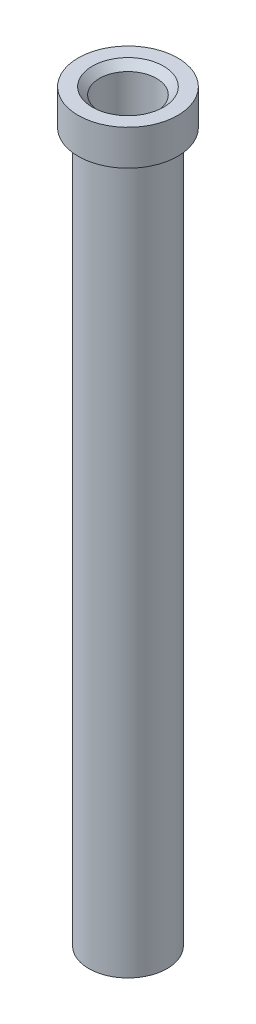
SolidWorks part; units mm, degrees
ref_plane "Front Plane" through (0, 0, 0) normal (0, 0, 1) x (1, 0, 0)
ref_plane "Top Plane" through (0, 0, 0) normal (0, 1, 0) x (1, 0, 0)
ref_plane "Right Plane" through (0, 0, 0) normal (1, 0, 0) x (0, 0, -1)
sketch "Sketch1" plane through (0, 0, 0) normal (0, 1, 0) x (1, 0, 0)
  circle A1 centre (0, 0) radius 2.8067
  dimension "D1" = 5.6134
extrude "Boss-Extrude1" add sketch "Sketch1" along normal blind 53.34
sketch "Sketch2" plane through (0, 53.34, 0) normal (0, 1, 0) x (1, 0, 0)
  point P0 (0, 0)
hole_wizard "#20 (0.161) Diameter Hole1" positions "3DSketch1" profile "Sketch4" hole size "#20" standard "ANSI Inch"
sketch3d "3DSketch1"
  point P0 (0, 53.34, 0)
sketch "Sketch4" plane through (0, 53.34, 0) normal (1, 0, 0) x (0, 0, 1)
  line L0 (0, 0) -> (0, 50.7586)
  line L1 (0, 50.7586) -> (2.0447, 49.53)
  line L2 (2.0447, 49.53) -> (2.0447, 0)
  line L5 (2.0447, 0) -> (0, 0)
  line L10 (0, 50.7586) -> (-2.0447, 49.53) construction
  line L11 (0, -6.35) -> (0, 107.95) construction
  dimension "Hole Dia." = 4.0894
  dimension "Hole Depth" = 49.53
  dimension "Drill Angle" = 118
sketch "Sketch5" plane through (0, 53.34, 0) normal (0, 1, 0) x (1, 0, 0)
  circle A1 centre (0, 0) radius 2.8067 construction
  circle A2 centre (0, 0) radius 3.5687
  circle A3 centre (0, 0) radius 3.5687
  circle A4 centre (0, 0) radius 2.8067
  dimension "D1" = 0.762
extrude "Boss-Extrude2" add sketch "Sketch5" against normal blind 2.54
chamfer "Chamfer1" distance 0.508 1 edges at (0, 53.34, 2.0447)
